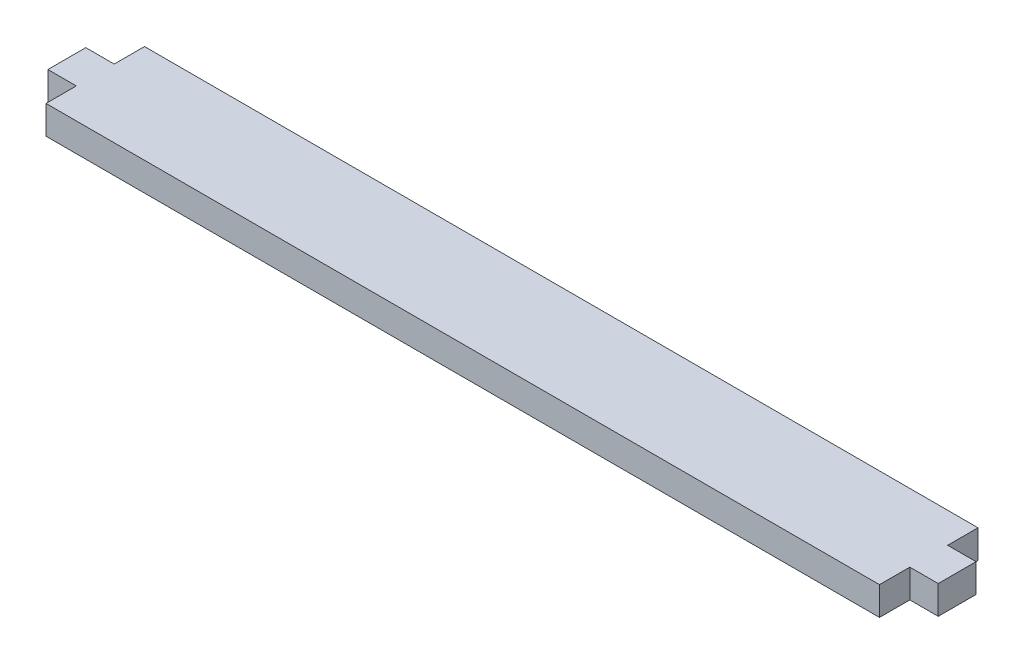
SolidWorks part; units mm, degrees
ref_plane "Front Plane" through (0, 0, 0) normal (0, 0, 1) x (1, 0, 0)
ref_plane "Top Plane" through (0, 0, 0) normal (0, 1, 0) x (1, 0, 0)
ref_plane "Right Plane" through (0, 0, 0) normal (1, 0, 0) x (0, 0, -1)
sketch "Sketch1" plane through (0, 0, 0) normal (0, 1, 0) x (1, 0, 0)
  line L1 (139.7, -16.51) -> (-139.7, -16.51)
  line L2 (139.7, -16.51) -> (139.7, 16.51)
  line L3 (139.7, 16.51) -> (-139.7, 16.51)
  line L4 (-139.7, -16.51) -> (-139.7, 16.51)
  line L5 (139.7, -16.51) -> (-139.7, 16.51) construction
  line L6 (139.7, 16.51) -> (-139.7, -16.51) construction
  point P0 (0, 0)
  dimension "D1" = 279.4
  dimension "D2" = 33.02
extrude "Boss-Extrude1" add sketch "Sketch1" along normal blind 9.525
sketch "Sketch2" plane through (139.7, 0, 0) normal (1, 0, 0) x (0, 0, -1)
  line L0 (-16.51, 0) -> (16.51, 0) construction
  line L1 (-6.35, 0) -> (6.35, 0)
  line L2 (-6.35, 0) -> (-6.35, 9.525)
  line L3 (-6.35, 9.525) -> (6.35, 9.525)
  line L4 (6.35, 0) -> (6.35, 9.525)
  line L5 (-16.51, 9.525) -> (16.51, 9.525) construction
  line L6 (-16.51, 9.525) -> (-16.51, 0) construction
  dimension "D1" = 12.7
  dimension "D2" = 10.16
extrude "Boss-Extrude2" add sketch "Sketch2" along normal blind 9.525
mirror "Mirror1" about plane through (0, 0, 0) normal (1, 0, 0) of "Boss-Extrude2"
sketch "Sketch3" plane through (0, 0, 0) normal (0, -1, 0) x (1, 0, 0)
  line L0 (-138.2612, -11.4174) -> (137.3788, -11.4174)
